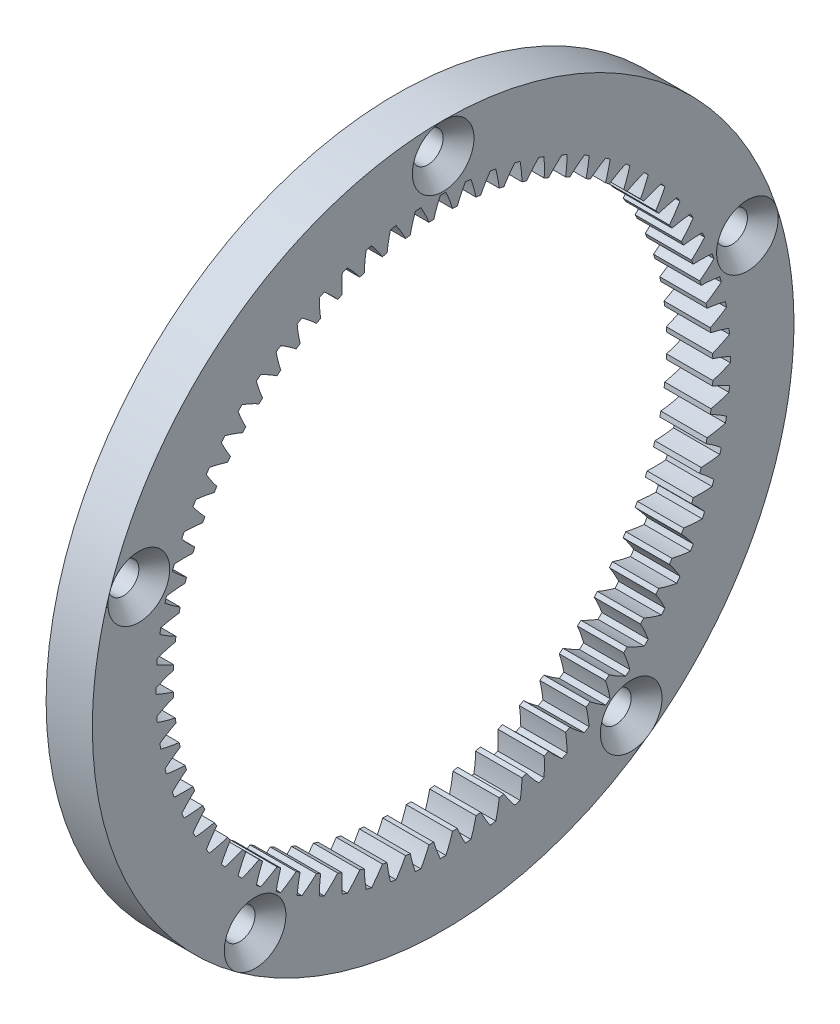
SolidWorks part; units mm, degrees
ref_plane "Plane1" through (0, 0, 0) normal (0, 0, 1) x (1, 0, 0)
ref_plane "Plane2" through (0, 0, 0) normal (0, 1, 0) x (1, 0, 0)
ref_plane "Plane3" through (0, 0, 0) normal (1, 0, 0) x (0, 0, -1)
sketch "HoldingSke" plane through (0, 0, 0) normal (0, 1, 0) x (1, 0, 0)
  line L0 (0, 0) -> (0.618, -1.9021)
  line L1 (-15, 0) -> (100, 0) construction
  line L2 (0, 0) -> (-2.1039, 2.3779)
  line L3 (0, 0) -> (-11.863, 4.5341)
  line L4 (0, 0) -> (2.6687, 8.2133)
  line L5 (0, 0) -> (-23.7986, -8.8762)
  line L6 (0, 0) -> (-10.5278, -7.1032)
  line L7 (-2.1039, 2.3779) -> (3.3635, 27.1825)
  line L8 (-76.2, 2.8779) -> (-54.61, 2.8779)
  line L9 (-71.009, 38.7566) -> (-53.1078, 45.2721)
  line L10 (-76.2, 71.12) -> (104.1128, 71.12)
  line L11 (0, 0) -> (-3, 0)
  line L12 (-76.2, 101.6) -> (-76.181, 101.6)
  line L13 (24.9733, 27.94) -> (52.9518, 28.4284)
  line L14 (24.9733, 27.94) -> (24.9743, 27.94)
  line L15 (24.9733, 27.94) -> (100.4006, 29.5858)
  circle A0 centre (0, 0) radius 22.75
  circle A1 centre (0, 0) radius 12.7
  circle A2 centre (0, 0) radius 12.7
  dimension "MHD" = 25.4
  dimension "Hub_dia" = 25.4
  dimension "Diameter" = 45.5
  dimension "Num_teeth" = 72
  dimension "Pitch_radius" = 180.3128
  dimension "Pitch" = 2
  dimension "Width" = 3
  dimension "Overall_len" = 25.4
  dimension "Show_teeth" = 72
  dimension "Thickness" = 12.7
  dimension "OAL" = 25.4001
  dimension "T_dim" = 21.59
  dimension "Ap" = 20
  dimension "H" = 19.05
  dimension "Backlash" = 0.019
  dimension "Addendum_fac" = 1
  dimension "Dedendum_fac" = 1.25
  dimension "Clearance_fac" = 0.25
  dimension "Dedendum_add" = 0.001
  dimension "Module" = 0.5
sketch "BasProSke" plane through (0, 0, 0) normal (0, 1, 0) x (1, 0, 0)
  line L0 (-10, 0) -> (60, 0) construction
  line L1 (0, 17.5) -> (0, 22.75)
  line L2 (0, 17.5) -> (3, 17.5)
  line L3 (3, 17.5) -> (3, 22.75)
  line L4 (3, 22.75) -> (0, 22.75)
  dimension "Diameter" = 45.5
  dimension "Thickness" = 3
  dimension "Inside_diameter" = 35
revolve "Base-Revolve" add sketch "BasProSke" angle 360 about L0
sketch "TooCutSke" plane through (0, 0, 0) normal (1, 0, 0) x (0, 0, -1)
  line L3 (0.4402, 17.9946) -> (0.4402, 53.6633) construction
  line L4 (0, 0) -> (0, 59.563) construction
  line L5 (0, 0) -> (-2.9804, 68.2625) construction
  line L6 (-8.0066, 14.8879) -> (37.1428, 16.8592) construction
  circle A0 centre (0, 0) radius 18 construction
  circle A1 centre (0, 0) radius 18.626 construction
  circle A2 centre (0, 0) radius 15.223 construction
  circle A3 centre (0, 0) radius 17.4746 construction
  arc A4 (0.6169, 17.4637) -> (0.1808, 18.6251) centre (-8.0066, 14.8879) ccw
  arc A5 (0.6169, 17.4637) -> (-0.6169, 17.4637) centre (0, 0) ccw
  arc A6 (0.1808, 18.6251) -> (-0.1808, 18.6251) centre (0, 0) ccw
  arc A7 (-0.1808, 18.6251) -> (-0.6169, 17.4637) centre (8.0066, 14.8879) ccw
  dimension "Pitch_dia" = 36
  dimension "Base_dia" = 30.446
  dimension "Root_dia" = 37.252
  dimension "Overcut_dia" = 34.9492
  dimension "Flank_rad" = 9
  dimension "Half_ang" = 2.5
  dimension "Half_CT" = 0.4402
extrude "ToothCut" cut sketch "TooCutSke" along normal through all
fillet "Breaks" [suppressed] radius 0.05
fillet "RootFillets" [suppressed] radius 0.126
pattern_circular "TeethCuts" count 72 over 360 about axis through (-10, 0, 0) along (1, 0, 0) of "RootFillets", "Breaks", "ToothCut"
sketch "Sketch1" plane through (3, 0, 0) normal (1, 0, 0) x (0, 0, -1)
  line L0 (0, 20.75) -> (0, 0) construction
  line L1 (0, 0) -> (-22.75, 0) construction
  circle A0 centre (0, 20.75) radius 1
  circle A1 centre (0, 0) radius 22.75 construction
  dimension "D2" = 2
  dimension "D1" = 90
  dimension "D3" = 20.75
extrude "Cut-Extrude1" cut sketch "Sketch1" against normal up to next
chamfer "Chamfer1" distance 1 angle 45 1 edges at (3, 20.75, -1)
pattern_circular "CirPattern1" count 5 over 360 about axis through (3, 0, 0) along (-1, 0, 0) of "Cut-Extrude1", "Chamfer1"
equation "' \"Module@HoldingSke\" = 6.35"
equation "' \"Num_teeth@HoldingSke\" = 24"
equation "' \"Ap@HoldingSke\" =  14.5"
equation "' \"Width@HoldingSke\" = 12"
equation "' \"Diameter@HoldingSke\" = 8 * 25.4"
equation "' \"Show_teeth@HoldingSke\" = 100"
equation "' \"Backlash@HoldingSke\" = 0.009 * 25.4"
equation "' \"Addendum_fac@HoldingSke\" = 1.0"
equation "' \"Dedendum_fac@HoldingSke\" = 1.25"
equation "' \"Dedendum_add@HoldingSke\" = 0.00005 * 25.4"
equation "' \"Clearance_fac@HoldingSke\" = 0.25"
equation "\"Pitch@HoldingSke\" = 1 / \"Module@HoldingSke\" "
equation "\"Overcut_dia@TooCutSke\" = (\"Num_teeth@HoldingSke\" - 2 * \"Addendum_fac@HoldingSke\") / \"Pitch@HoldingSke\" - 0.002 * 25.4"
equation "\"Pitch_dia@TooCutSke\" = \"Num_teeth@HoldingSke\" / \"Pitch@HoldingSke\""
equation "\"Base_dia@TooCutSke\" = \"Num_teeth@HoldingSke\" / \"Pitch@HoldingSke\" * cos((\"Ap@HoldingSke\"  * 3.14159265 / 180)) * 0.90"
equation "\"Root_dia@TooCutSke\" = \"Num_teeth@HoldingSke\"  / \"Pitch@HoldingSke\" + 2 *  \"Dedendum_fac@HoldingSke\"/ \"Pitch@HoldingSke\" + \"Dedendum_add@HoldingSke\" * 2"
equation "\"Half_ang@TooCutSke\" = 180 / \"Num_teeth@HoldingSke\""
equation "\"Half_CT@TooCutSke\" = \"Num_teeth@HoldingSke\" / \"Pitch@HoldingSke\" * sin((3.14159265 / 2 / \"Num_teeth@HoldingSke\")) / 2 + 10 * \"Backlash@HoldingSke\" / 4"
equation "\"Flank_rad@TooCutSke\" = \"Num_teeth@HoldingSke\" / \"Pitch@HoldingSke\" / 4"
equation "\"Radius@RootFillets\"= \"Clearance_fac@HoldingSke\" / \"Pitch@HoldingSke\" + \"Dedendum_add@HoldingSke\""
equation "\"Break_rad@Breaks\" = 0.02 / \"Pitch@HoldingSke\" * 5"
equation "\"Num_teeth@TeethCuts\" = int( \"Show_teeth@HoldingSke\" ) + 1"
equation "\"Num_teeth@TeethCuts\" = ((sgn( \"Num_teeth@TeethCuts\" - \"Num_teeth@HoldingSke\" )-1)*( \"Num_teeth@TeethCuts\" - \"Num_teeth@HoldingSke\" ))/-2+ \"Num_teeth@HoldingSke\""
equation "\"Num_teeth@TeethCuts\" = ((sgn( \"Num_teeth@TeethCuts\" - 2.0)+1)*( \"Num_teeth@TeethCuts\" - 2.0))/2 +2.0"
equation "\"Angle@TeethCuts\" = 360.0 / \"Num_teeth@HoldingSke\""
equation "\"Diameter@BasProSke\" = \"Num_teeth@HoldingSke\"  / \"Pitch@HoldingSke\" + 2 *  \"Dedendum_fac@HoldingSke\"/ \"Pitch@HoldingSke\" + \"Dedendum_add@HoldingSke\" * 2 + 0.002 * 25.4"
equation "\"Diameter@BasProSke\" = ((sgn( \"Diameter@BasProSke\"  - \"Diameter@HoldingSke\" )+1)*( \"Diameter@BasProSke\"  - \"Diameter@HoldingSke\" ))/2 + \"Diameter@HoldingSke\""
equation "\"Inside_diameter@BasProSke\" =  (\"Num_teeth@HoldingSke\" - 2 * \"Addendum_fac@HoldingSke\") / \"Pitch@HoldingSke\" "
equation "\"Thickness@BasProSke\"  = \"Width@HoldingSke\""
